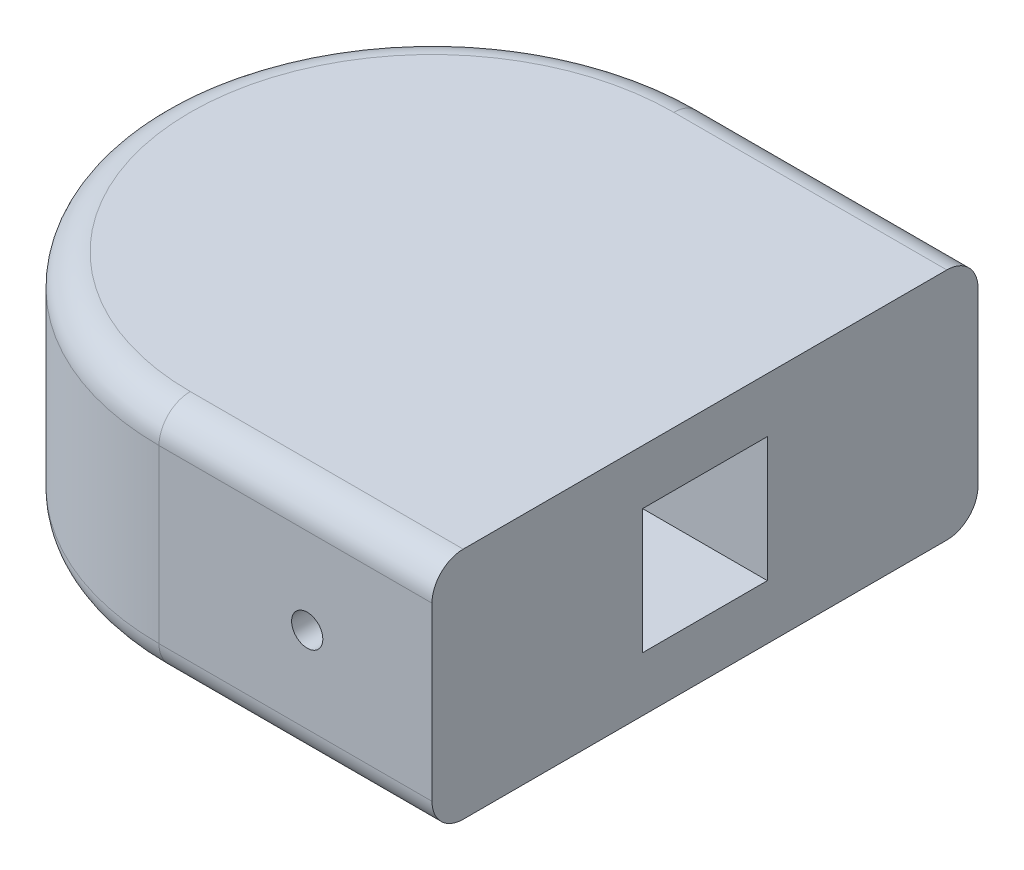
SolidWorks part; units mm, degrees
ref_plane "Front Plane" through (0, 0, 0) normal (0, 0, 1) x (1, 0, 0)
ref_plane "Top Plane" through (0, 0, 0) normal (0, 1, 0) x (1, 0, 0)
ref_plane "Right Plane" through (0, 0, 0) normal (1, 0, 0) x (0, 0, -1)
sketch "Sketch1" plane through (0, 0, 0) normal (0, 1, 0) x (1, 0, 0)
  line L1 (0, 0) -> (44.45, 0)
  line L2 (0, 0) -> (0, 44.45)
  line L3 (0, 44.45) -> (44.45, 44.45)
  line L4 (44.45, 0) -> (44.45, 44.45)
  line L5 (22.225, 44.45) -> (22.225, 0)
  arc A0 (22.225, 44.45) -> (22.225, 0) centre (22.225, 22.225) ccw
  dimension "D1" = 44.45
  dimension "D2" = 44.45
extrude "Main body extrude" add sketch "Sketch1" along normal blind 19.05 contours L5 A0 | L3 L5 L1 L4 region at (33.3375, 0, -22.225) region at (12.7924, 0, -22.225)
sketch "Sketch2" plane through (44.45, 0, 0) normal (1, 0, 0) x (0, 0, -1)
  line L0 (22.225, 19.05) -> (22.225, 0) construction
  line L1 (0, 19.05) -> (44.45, 19.05) construction
  line L2 (0, 0) -> (44.45, 0) construction
  line L3 (44.45, 9.525) -> (22.225, 9.525) construction
  line L4 (44.45, 19.05) -> (44.45, 0) construction
  line L6 (17.145, 14.605) -> (27.305, 14.605)
  line L7 (17.145, 14.605) -> (17.145, 4.445)
  line L8 (17.145, 4.445) -> (27.305, 4.445)
  line L9 (27.305, 14.605) -> (27.305, 4.445)
  line L10 (17.145, 14.605) -> (27.305, 4.445) construction
  line L11 (17.145, 4.445) -> (27.305, 14.605) construction
  dimension "D1" = 10.16
  dimension "D2" = 10.16
extrude "Upper foot connection cut" cut sketch "Sketch2" against normal blind 15.24
sketch "Sketch3" plane through (0, 0, 0) normal (0, 0, 1) x (1, 0, 0)
  line L0 (44.45, 9.525) -> (29.21, 9.525) construction
  line L1 (44.45, 19.05) -> (44.45, 0) construction
  line L2 (29.21, 9.525) -> (34.29, 9.525)
  circle A0 centre (34.29, 9.525) radius 1.27
  dimension "D3" = 2.54
  dimension "D1" = 15.24
  dimension "D2" = 5.08
fillet "Fillet1" radius 2.54 6 edges at (0, 0, -22.225) (0, 19.05, -22.225) (33.3375, 19.05, -44.45) (33.3375, 0, -44.45) (33.3375, 0, 0) (33.3375, 19.05, 0)
extrude "Pinhole cut" cut sketch "Sketch3" against normal blind 64.516 contours A0
equation "\"heelLength\"=1.75"
equation "\"D1@Sketch1\"=\"heelLength\""
equation "\"heelWidth\"=1.75"
equation "\"D2@Sketch1\"=\"heelWidth\""
equation "\"heelHeight\"=0.75"
equation "\"D1@Main body extrude\"=\"heelHeight\""
